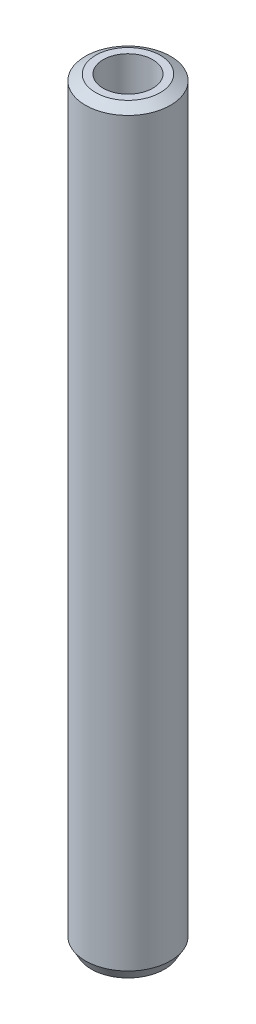
SolidWorks part; units mm, degrees
ref_plane "Front Plane" through (0, 0, 0) normal (0, 0, 1) x (1, 0, 0)
ref_plane "Top Plane" through (0, 0, 0) normal (0, 1, 0) x (1, 0, 0)
ref_plane "Right Plane" through (0, 0, 0) normal (1, 0, 0) x (0, 0, -1)
sketch "Sketch1" plane through (0, 0, 0) normal (0, 1, 0) x (1, 0, 0)
  circle A0 centre (0, 0) radius 10
  dimension "SHAFT_OD" = 20
extrude "Boss-Extrude1" add sketch "Sketch1" along normal blind 177.9537
sketch "Sketch2" plane through (0, 0, 0) normal (0, 1, 0) x (1, 0, 0)
  circle A0 centre (0, 0) radius 5.8261
  dimension "BORE_D" = 11.6522
extrude "Cut-Extrude1" cut sketch "Sketch2" along normal through all
chamfer "Chamfer1" distance 1.3825 angle 60 2 edges at (0, 177.9537, 10) (0, 0, 10) first distance on face at (0, 177.9537, 10) first distance on face at (0, 0, 5.8261)
